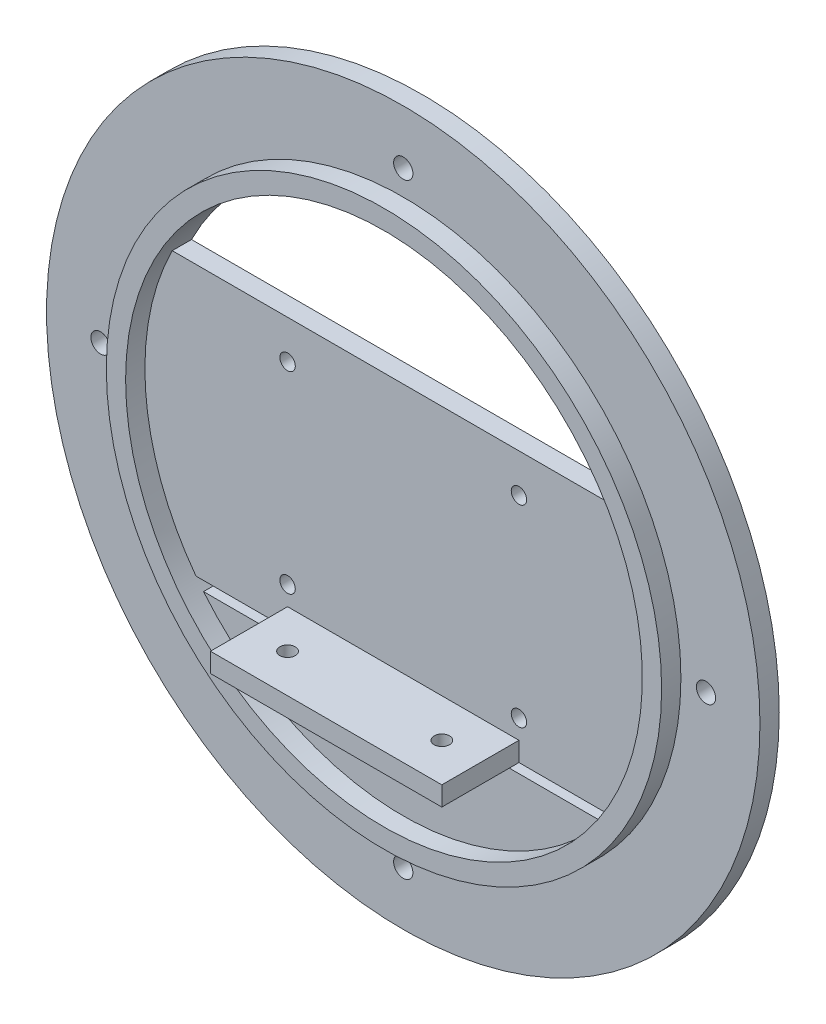
SolidWorks part; units mm, degrees
ref_plane "Front Plane" through (0, 0, 0) normal (0, 0, 1) x (1, 0, 0)
ref_plane "Top Plane" through (0, 0, 0) normal (0, 1, 0) x (1, 0, 0)
ref_plane "Right Plane" through (0, 0, 0) normal (1, 0, 0) x (0, 0, -1)
sketch "Sketch1" plane through (0, 0, 0) normal (0, 0, 1) x (1, 0, 0)
  circle A0 centre (0, 0) radius 92.5
  dimension "D1" = 185
extrude "Boss-Extrude1" add sketch "Sketch1" along normal blind 5
sketch "Sketch2" plane through (0, 0, 5) normal (0, 0, 1) x (1, 0, 0)
  circle A0 centre (0, 0) radius 72
  dimension "D1" = 144
extrude "Boss-Extrude2" add sketch "Sketch2" along normal blind 5
sketch "Sketch3" plane through (0, 0, 0) normal (0, 0, -1) x (-1, 0, 0)
  circle A0 centre (0, 0) radius 67
  dimension "D1" = 134
extrude "Cut-Extrude1" cut sketch "Sketch3" against normal through all
sketch "Sketch4" plane through (0, 0, 0) normal (0, 0, -1) x (-1, 0, 0)
  line L0 (92.5, 0) -> (-92.5, 0) construction
  line L5 (0, -92.5) -> (0, 92.5) construction
  line L11 (70, 30) -> (-70, 30)
  line L12 (70, 30) -> (70, -40)
  line L13 (70, -40) -> (-70, -40)
  line L14 (-70, 30) -> (-70, -40)
  circle A0 centre (0, 0) radius 92.5 construction
  dimension "D1" = 70
  dimension "D2" = 40
  dimension "D3" = 30
  dimension "D4" = 140
  dimension "D5" = 70
  dimension "D6" = 70
extrude "Boss-Extrude3" add sketch "Sketch4" against normal blind 5
sketch "Sketch6" plane through (0, 0, 5) normal (0, 0, 1) x (1, 0, 0)
  line L0 (0, -40) -> (0, 30) construction
  line L1 (53.7494, -40) -> (-53.7494, -40) construction
  line L2 (-59.9083, 30) -> (59.9083, 30) construction
  line L3 (-92.5, 0) -> (92.5, 0) construction
  line L5 (30, -40) -> (-30, -40)
  line L6 (30, -40) -> (30, -35)
  line L7 (30, -35) -> (-30, -35)
  line L8 (-30, -40) -> (-30, -35)
  circle A0 centre (0, 0) radius 92.5 construction
  dimension "D1" = 30
  dimension "D2" = 60
  dimension "D3" = 30
  dimension "D4" = 5
extrude "Boss-Extrude4" add sketch "Sketch6" along normal blind 20
fillet "Fillet1" radius 2.5 1 edges at (0, -40, 0)
sketch "Sketch7" plane through (0, 0, 0) normal (0, 0, -1) x (-1, 0, 0)
  line L0 (0, 92.5) -> (0, -92.5) construction
  line L1 (92.5, 0) -> (-92.5, 0) construction
  line L3 (-55, -42.5) -> (55, -42.5)
  line L4 (-55, -42.5) -> (-55, -67.5)
  line L5 (-55, -67.5) -> (55, -67.5)
  line L6 (55, -42.5) -> (55, -67.5)
  circle A0 centre (0, 0) radius 92.5 construction
  dimension "D1" = 110
  dimension "D2" = 5
  dimension "D3" = 25
  dimension "D4" = 55
extrude "Boss-Extrude5" add sketch "Sketch7" against normal blind 5
sketch "Sketch8" plane through (0, 0, 0) normal (0, 0, -1) x (-1, 0, 0)
  line L0 (51.7953, -42.5) -> (-51.7953, -42.5) construction
  line L1 (-30, -42.5) -> (30, -42.5)
  line L2 (-30, -42.5) -> (-30, -47.5)
  line L3 (-30, -47.5) -> (30, -47.5)
  line L4 (30, -42.5) -> (30, -47.5)
  line L5 (0, 92.5) -> (0, -92.5) construction
  circle A0 centre (0, 0) radius 92.5 construction
  dimension "D1" = 60
  dimension "D2" = 5
  dimension "D3" = 30
  dimension "D4" = 30
extrude "Boss-Extrude6" add sketch "Sketch8" along normal blind 30
sketch "Sketch9" plane through (0, -35, 0) normal (0, 1, 0) x (1, 0, 0)
  line L0 (0, 30) -> (0, -25) construction
  line L1 (-30, 30) -> (30, 30) construction
  line L2 (30, -25) -> (-30, -25) construction
  line L3 (30, -25) -> (30, -5) construction
  line L4 (-30, -25) -> (-30, -5) construction
  circle A0 centre (-20, -15) radius 2
  circle A1 centre (20, -15) radius 2
  dimension "D1" = 4
  dimension "D2" = 4
  dimension "D4" = 10
  dimension "D3" = 10
  dimension "D5" = 10
  dimension "D6" = 10
extrude "Cut-Extrude2" cut sketch "Sketch9" against normal up to surface (5 mm away) up to face at (0, -40, 9.375)
sketch "Sketch10" plane through (0, -42.5, 0) normal (0, 1, 0) x (1, 0, 0)
  line L0 (0, 30) -> (0, 0) construction
  line L1 (-30, 30) -> (30, 30) construction
  line L2 (30, 15) -> (-30, 15) construction
  line L3 (30, 30) -> (30, 0) construction
  line L4 (-30, 30) -> (-30, 0) construction
  line L5 (92.5, 0) -> (-92.5, 0) construction
  circle A0 centre (-20, 20) radius 2
  circle A1 centre (20, 20) radius 2
  dimension "D3" = 4
  dimension "D4" = 4
  dimension "D1" = 20
  dimension "D2" = 20
  dimension "D5" = 10
  dimension "D6" = 10
extrude "Cut-Extrude3" cut sketch "Sketch10" against normal up to surface (5 mm away) up to face at (0, -47.5, -15)
sketch "Sketch11" plane through (0, 0, 0) normal (0, 0, -1) x (-1, 0, 0)
  line L0 (-92.5, 0) -> (92.5, 0) construction
  line L1 (0, -92.5) -> (0, 90.9687) construction
  circle A0 centre (0, 0) radius 92.5 construction
  circle A1 centre (-30, -30) radius 2
  circle A2 centre (-30, 20) radius 2
  circle A3 centre (30, 20) radius 2
  circle A4 centre (30, -30) radius 2
  dimension "D7" = 4
  dimension "D8" = 4
  dimension "D9" = 4
  dimension "D10" = 4
  dimension "D1" = 60
  dimension "D2" = 50
  dimension "D3" = 30
  dimension "D4" = 20
  dimension "D5" = 30
  dimension "D6" = 30
extrude "Cut-Extrude4" cut sketch "Sketch11" against normal up to surface (5 mm away) up to face at (0, -21.4681, 5)
sketch "Sketch12" plane through (0, 0, 0) normal (0, 0, -1) x (-1, 0, 0)
  line L0 (0, -92.5) -> (0, 92.5) construction
  line L1 (92.5, 0) -> (-92.5, 0) construction
  circle A0 centre (0, 0) radius 92.5 construction
  circle A1 centre (0, -78.5) radius 2.5
  circle A2 centre (-78.5, 0) radius 2.5
  circle A3 centre (0, 78.5) radius 2.5
  circle A4 centre (78.5, 0) radius 2.5
  dimension "D1" = 5
  dimension "D2" = 5
  dimension "D3" = 5
  dimension "D4" = 5
  dimension "D5" = 78.5
  dimension "D6" = 78.5
  dimension "D7" = 78.5
  dimension "D8" = 78.5
extrude "Cut-Extrude5" cut sketch "Sketch12" against normal up to surface (5 mm away) up to face at (72, 0, 5)
